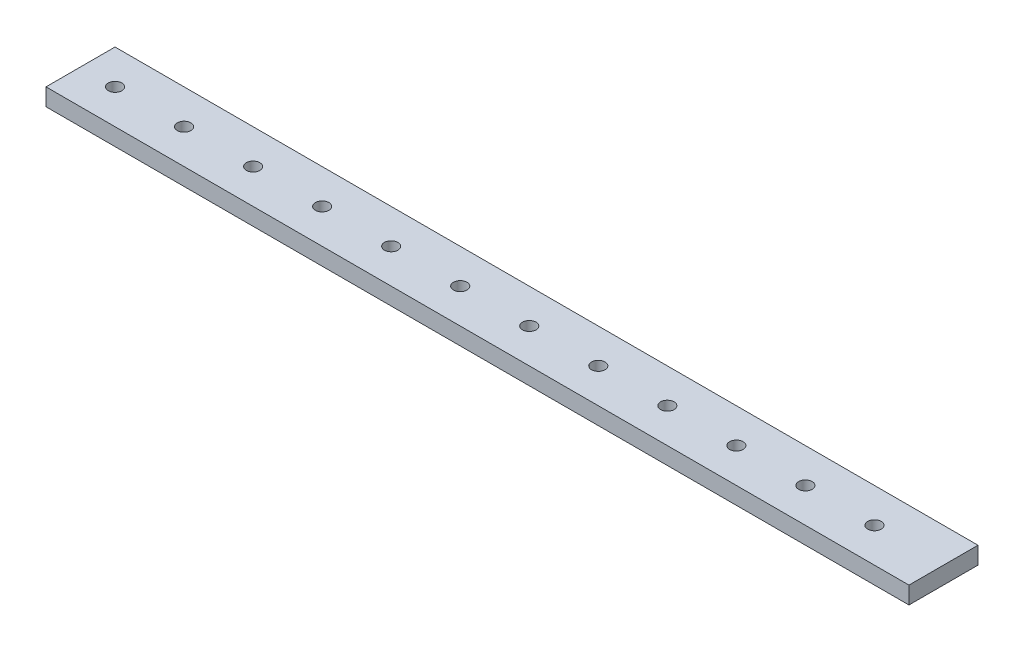
SolidWorks part; units mm, degrees
ref_plane "Front Plane" through (0, 0, 0) normal (0, 0, 1) x (1, 0, 0)
ref_plane "Top Plane" through (0, 0, 0) normal (0, 1, 0) x (1, 0, 0)
ref_plane "Right Plane" through (0, 0, 0) normal (1, 0, 0) x (0, 0, -1)
sketch "Sketch1" plane through (0, 0, 0) normal (0, 1, 0) x (1, 0, 0)
  line L1 (0, 0) -> (317.5, 0)
  line L2 (0, 0) -> (0, 25.4)
  line L3 (0, 25.4) -> (317.5, 25.4)
  line L4 (317.5, 0) -> (317.5, 25.4)
  dimension "D1" = 25.4
  dimension "D2" = 317.5
extrude "Boss-Extrude1" add sketch "Sketch1" along normal blind 6.35
sketch "Sketch2" plane through (0, 6.35, 0) normal (0, 1, 0) x (1, 0, 0)
  line L0 (317.5, 12.7) -> (0, 12.7) construction
  line L1 (317.5, 0) -> (317.5, 25.4) construction
  line L2 (0, 25.4) -> (0, 0) construction
  circle A0 centre (292.1, 12.7) radius 2.4892
  circle A1 centre (266.7, 12.7) radius 2.4892
  circle A2 centre (241.3, 12.7) radius 2.4892
  circle A3 centre (215.9, 12.7) radius 2.4892
  circle A4 centre (190.5, 12.7) radius 2.4892
  circle A5 centre (165.1, 12.7) radius 2.4892
  circle A6 centre (139.7, 12.7) radius 2.4892
  circle A7 centre (114.3, 12.7) radius 2.4892
  circle A8 centre (88.9, 12.7) radius 2.4892
  circle A9 centre (63.5, 12.7) radius 2.4892
  circle A10 centre (38.1, 12.7) radius 2.4892
  circle A11 centre (12.7, 12.7) radius 2.4892
  dimension "D1" = 25.4
  dimension "D2" = 4.9784
  dimension "D3" = 12
extrude "Cut-Extrude1" cut sketch "Sketch2" against normal through all both
